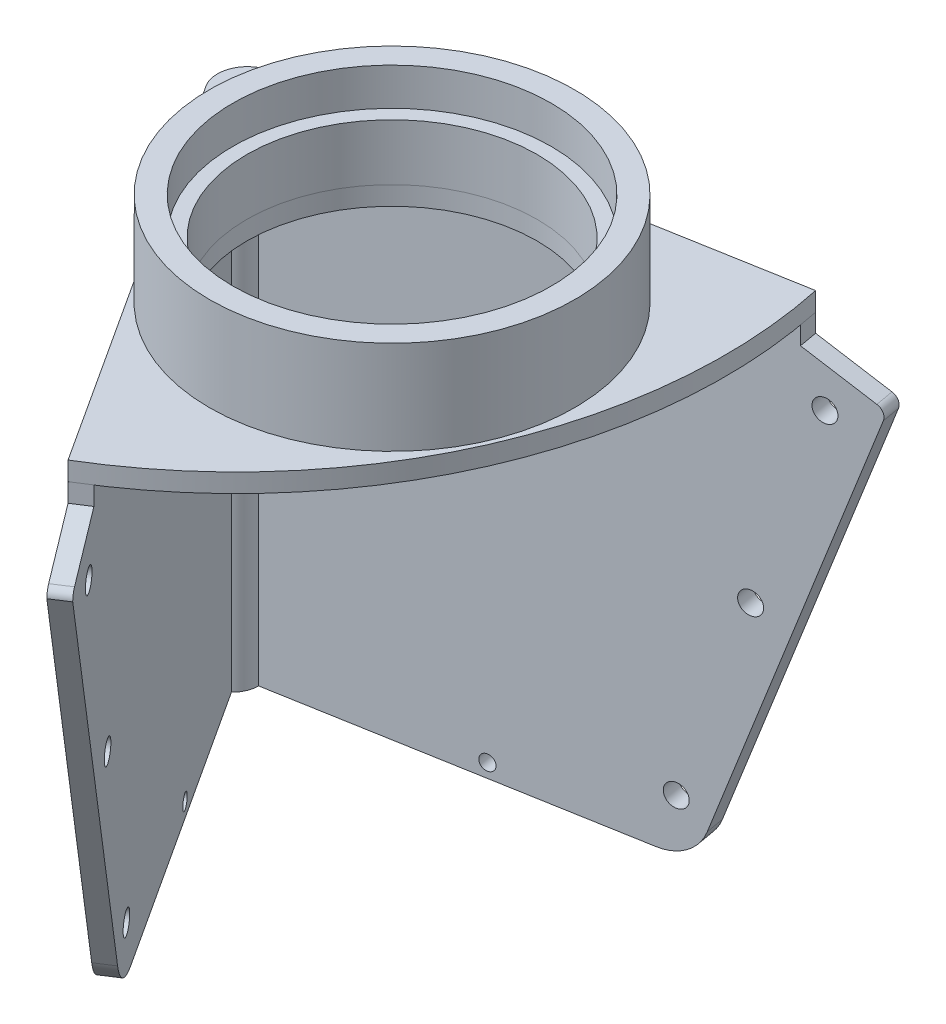
SolidWorks part; units mm, degrees
note: The reader was unsure of these and kept them because the rebuilt part matched: shared geometry of "Sketch5<3>", "Sketch5<4>".
ref_plane "Front Plane" through (0, 0, 0) normal (0, 0, 1) x (1, 0, 0)
ref_plane "Top Plane" through (0, 0, 0) normal (0, 1, 0) x (1, 0, 0)
ref_plane "Right Plane" through (0, 0, 0) normal (1, 0, 0) x (0, 0, -1)
sketch "Sketch1" plane through (3.1591, 0, 17.9161) normal (-0.1736, 0, -0.9848) x (-0.9848, 0, 0.1736)
  line L0 (90.9457, -13.5582) -> (72.595, -13.5582)
  line L1 (70.2458, -11.9132) -> (62.123, 10.404) construction
  line L2 (70.2458, -11.9132) -> (62.123, 10.404)
  line L3 (62.4218, 11.0448) -> (65.9457, 12.3274)
  line L4 (65.9457, 12.3274) -> (65.9457, 13.3274)
  line L5 (65.9457, 13.3274) -> (66.9457, 13.3274)
  line L10 (90.9457, -12.0582) -> (90.9457, -13.5582)
  line L11 (90.9457, -12.0582) -> (90.9457, 13.3274)
  line L12 (66.9457, 13.3274) -> (90.9457, 13.3274)
  arc A0 (72.595, -13.5582) -> (70.2458, -11.9132) centre (72.595, -11.0582) cw
  arc A1 (70.2458, -11.9132) -> (72.595, -13.5582) centre (72.595, -11.0582) ccw construction
  arc A2 (62.123, 10.404) -> (62.4218, 11.0448) centre (62.5928, 10.575) cw
  circle A7 centre (64.816, 9.7887) radius 0.6
  circle A8 centre (68.2465, -0.5071) radius 0.6
  circle A9 centre (71.677, -10.8029) radius 0.6
  circle A10 centre (80.3897, -12.8204) radius 0.4
  line M17 (90.9457, -12.0582) -> (75.2753, -12.0582)
  line M18 (75.2753, -12.0582) -> (74.5615, -11.3443)
  line M19 (74.5615, -11.3443) -> (66.9457, 9.5799)
  line M20 (66.9457, 9.5799) -> (66.9457, 13.3274)
  line M21 (66.9457, 13.3274) -> (65.9457, 13.3274)
  line M22 (65.9457, 13.3274) -> (65.9457, 12.3274)
  line M23 (65.9457, 12.3274) -> (62.4218, 11.0448)
  arc M24 (62.4218, 11.0448) -> (62.123, 10.404) centre (62.5928, 10.575) ccw
  line M25 (62.123, 10.404) -> (70.2458, -11.9132)
  arc M26 (70.2458, -11.9132) -> (72.595, -13.5582) centre (72.595, -11.0582) ccw
  line M27 (72.595, -13.5582) -> (90.9457, -13.5582)
  line M28 (90.9457, -13.5582) -> (90.9457, -12.0582)
  circle M29 centre (71.677, -10.8029) radius 0.5
  circle M30 centre (80.3897, -12.8204) radius 0.3
  circle M31 centre (68.2465, -0.5071) radius 0.5
  circle M32 centre (64.816, 9.7887) radius 0.5
  dimension "D1" = 1.2
  dimension "D2" = 1.2
  dimension "D3" = 1.2
  dimension "D4" = 0.8
extrude "Boss-Extrude2" add sketch "Sketch1" along normal blind 1 contours L12 L11 M20 M19 M18 M17 | M28 M17 M18 M19 M20 M21 M22 M23 M24 M25 M26 M27 M30 M32 M31 M29
sketch "Sketch2" plane through (0, -13.5582, 0) normal (0, -1, 0) x (-1, 0, 0)
  line L0 (86.4049, -33.7086) -> (86.4049, -32.7086)
  line L1 (86.8451, -34.721) -> (87.5764, -35.403)
  arc A0 (86.8451, -34.721) -> (86.4049, -33.7086) centre (87.7891, -33.7086) cw
  arc A1 (86.4049, -32.7086) -> (87.5764, -35.403) centre (86.3765, -34.3229) cw
  dimension "D1" = 1
  dimension "D2" = 1
  dimension "D3" = 1
extrude "Boss-Extrude3" add sketch "Sketch2" against normal blind 26.85 separate body
sketch "Sketch3" plane through (-76.9437, 0, 49.9678) normal (-0.8387, 0, 0.5446) x (0.5446, 0, 0.8387)
  line L0 (-18.1798, -13.5582) -> (0.1709, -13.5582)
  line L1 (2.5201, -11.9132) -> (10.6731, 10.575)
  line L2 (10.3441, 11.0448) -> (6.8202, 12.3274)
  line L3 (6.8202, 12.3274) -> (6.8202, 13.3274)
  line L4 (6.8202, 13.3274) -> (5.8202, 13.3274)
  line L5 (5.8202, 13.3274) -> (-18.1798, 13.2918)
  line L6 (-18.1798, 13.2918) -> (-18.1798, -13.5582)
  arc A0 (0.1709, -13.5582) -> (2.5201, -11.9132) centre (0.1709, -11.0582) ccw
  arc A1 (10.6429, 10.404) -> (10.3441, 11.0448) centre (10.1731, 10.575) ccw construction
  arc A2 (10.3441, 11.0448) -> (10.6731, 10.575) centre (10.1731, 10.575) cw
  circle A4 centre (4.3389, -0.7249) radius 0.6
  circle A5 centre (7.7694, 9.5709) radius 0.6
  circle A6 centre (0.9084, -11.0207) radius 0.6
  circle A7 centre (-9.7379, -12.7799) radius 0.4
  circle M10 centre (-9.7379, -12.7799) radius 0.3
  circle M11 centre (0.9084, -11.0207) radius 0.5
  circle M12 centre (7.7694, 9.5709) radius 0.5
  circle M13 centre (4.3389, -0.7249) radius 0.5
  line M14 (5.8202, 9.5799) -> (-1.7956, -11.3443)
  line M15 (-1.7956, -11.3443) -> (-2.5094, -12.0582)
  line M16 (-2.5094, -12.0582) -> (-18.1798, -12.0582)
  line M17 (-18.1798, -12.0582) -> (-18.1798, -13.5582)
  line M18 (-18.1798, -13.5582) -> (0.1709, -13.5582)
  arc M19 (0.1709, -13.5582) -> (2.5201, -11.9132) centre (0.1709, -11.0582) ccw
  arc M21 (10.6429, 10.404) -> (10.3441, 11.0448) centre (10.1731, 10.575) ccw
  line M22 (10.3441, 11.0448) -> (6.8202, 12.3274)
  line M23 (6.8202, 12.3274) -> (6.8202, 13.3274)
  line M24 (6.8202, 13.3274) -> (5.8202, 13.3274)
  line M25 (5.8202, 13.3274) -> (5.8202, 9.5799)
  dimension "D1" = 1.2
  dimension "D2" = 1.2
  dimension "D3" = 1.2
  dimension "D4" = 0.8
extrude "Boss-Extrude4" add sketch "Sketch3" along normal blind 1 contours L5 L6 M16 M15 M14 M25 | L1 M19 M21 M22 M23 M24 M25 M14 M15 M16 M17 M18 M11 M13 M12 M10
sketch "Sketch4" plane through (-0.0108, 13.3188, -0.0166) normal (-0.0008, 1, -0.0012) x (1, 0.0008, 0)
  line L0 (-74.057, -56.2489) -> (-87.6492, -35.3188)
  line L1 (-74.6017, -55.4102) -> (-87.673, -35.2821) construction
  line L2 (-86.5678, -32.7404) -> (-61.9476, -28.3992)
  line L3 (-61.9476, -28.3992) -> (-86.5678, -32.7404) construction
  line L6 (-86.5895, -32.7069) -> (-86.5678, -32.7404) construction
  line L7 (-74.057, -56.2489) -> (-73.2184, -55.7043) construction
  arc A1 (-87.6492, -35.3188) -> (-86.5678, -32.7404) centre (-86.3672, -34.3405) cw
  arc A2 (-74.057, -56.2489) -> (-61.9476, -28.3992) centre (-87.4792, -33.8552) ccw
  ellipse E1 centre (-86.3657, -34.3394) end of major axis (-85.0117, -33.4601) minor radius 1.6145 (-86.3942, -32.7251) -> (-87.6492, -35.3188) ccw construction
  ellipse E2 centre (-87.3798, -33.8976) end of major axis (-65.5743, -19.737) minor radius 26 (-73.2192, -55.703) -> (-61.7748, -29.3827) ccw construction
extrude "Boss-Extrude5" add sketch "Sketch4" along normal blind 1
sketch "Sketch5" plane through (-0.0116, 14.3188, -0.0178) normal (-0.0008, 1, -0.0012) x (1, 0.0008, 0)
  line L0 (-87.8543, -33.7168) -> (-63.5365, -44.2658) construction
  circle A0 centre (-72.6974, -40.2918) radius 8.5
  arc A1 (-86.5678, -32.7404) -> (-87.6492, -35.3188) centre (-86.3672, -34.3405) ccw construction
  arc A2 (-74.057, -56.2489) -> (-61.9476, -28.3992) centre (-87.4792, -33.8552) ccw construction
  circle A3 centre (-72.6974, -40.2918) radius 9.75
  circle A4 centre (-72.6974, -40.2918) radius 7.75
  dimension "D1" = 1.25
  dimension "D2" = 0.75
extrude "Boss-Extrude6" add sketch "Sketch5" along normal blind 5
extrude "Boss-Extrude7" add sketch "Sketch5<3>" along normal blind 3 from offset 0 separate body
sketch "Sketch5<3>" plane through (-0.0116, 14.3188, -0.0178) normal (-0.0008, 1, -0.0012) x (1, 0.0008, 0) same geometry as "Sketch5"
extrude "Cut-Extrude1" cut sketch "Sketch5<4>" against normal blind 3 contours L0 A4 | A4 L0
sketch "Sketch5<4>" plane through (-0.0116, 14.3188, -0.0178) normal (-0.0008, 1, -0.0012) x (1, 0.0008, 0) same geometry as "Sketch5"
